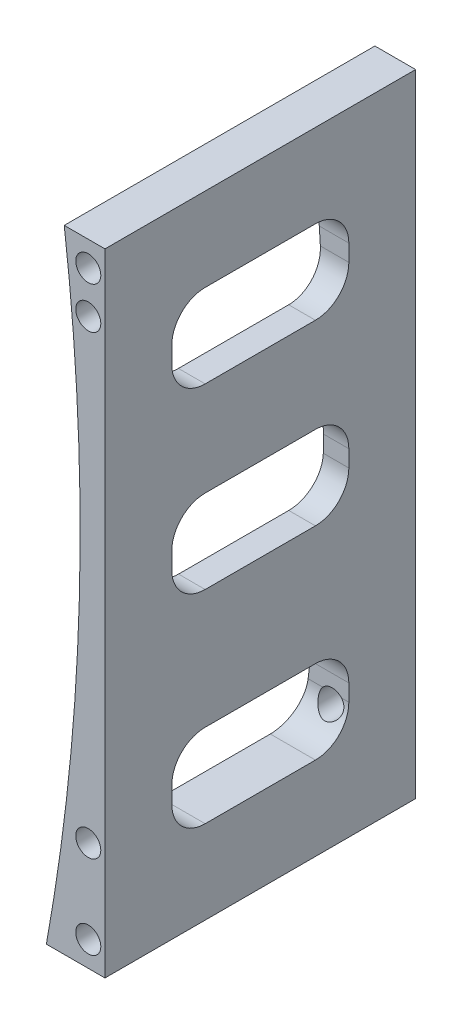
SolidWorks part; units mm, degrees
material "ABS"
ref_plane "Plano frontal" through (0, 0, 0) normal (0, 0, 1) x (1, 0, 0)
ref_plane "Plano superior" through (0, 0, 0) normal (0, 1, 0) x (1, 0, 0)
ref_plane "Plano direito" through (0, 0, 0) normal (1, 0, 0) x (0, 0, -1)
sketch "Esboço1" plane through (0, 0, 0) normal (0, 0, 1) x (1, 0, 0)
  line L0 (10, 0) -> (20, 0)
  line L1 (-20, 0) -> (-10, 0)
  line L2 (-16.3694, 93.6521) -> (-16.5765, 95.0244)
  arc A0 (-10, 0) -> (10, 0) centre (0, 0) ccw
  arc A1 (20, 0) -> (14.8299, 81.415) centre (263.5691, 56.3389) cw
  arc A2 (-20, 0) -> (-16.3694, 93.6521) centre (-263.5691, 56.3389) ccw
  arc A3 (14.8299, 81.415) -> (-16.4879, 94.4373) centre (3.2416, 97.7156) ccw
  dimension "D1" = 20
  dimension "D5" = 250
  dimension "D6" = 250
  dimension "D2" = 40
extrude "Ressalto-extrusão1" add sketch "Esboço1" along normal blind 37.2 contours A1 A3 L2 A2 L1 A0 L0 region at (0.9197, 55.6964, 0)
fillet "Filete3" radius 10 2 edges at (20, 0, 18.6) (-20, 0, 18.6)
fillet "Filete4" radius 10 2 edges at (-10, 0, 18.6) (10, 0, 18.6)
sketch "Esboço3" plane through (0, 0, 37.2) normal (0, 0, 1) x (1, 0, 0)
  line L1 (-34.3661, -10.4864) -> (30.1278, -10.4864)
  line L2 (-34.3661, -10.4864) -> (-34.3661, 11.5417)
  line L3 (-34.3661, 11.5417) -> (30.1278, 11.5417)
  line L4 (30.1278, -10.4864) -> (30.1278, 11.5417)
  dimension "D1" = 0
extrude "Corte-extrusão2" cut sketch "Esboço3" against normal through all
sketch "Esboço4" plane through (0, 0, 37.2) normal (0, 0, 1) x (1, 0, 0)
  line L0 (17.6155, 11.5417) -> (-17.6155, 11.5417) construction
  line L1 (-10.5979, 11.5417) -> (44.491, 11.5417)
  line L2 (-10.5979, 11.5417) -> (-10.5979, 134.6613)
  line L3 (-10.5979, 134.6613) -> (44.491, 134.6613)
  line L4 (44.491, 11.5417) -> (44.491, 134.6613)
  arc A0 (-17.6155, 11.5417) -> (-16.3694, 93.6521) centre (-263.5691, 56.3389) ccw construction
  point P9 (-13.5979, 52.5454)
  dimension "D1" = 3
extrude "Corte-extrusão3" cut sketch "Esboço4" against normal through all
sketch "Esboço5" plane through (0, 0, 37.2) normal (0, 0, 1) x (1, 0, 0)
  line L1 (-10.5979, 112.154) -> (-22.7536, 112.154)
  line L2 (-10.5979, 112.154) -> (-10.5979, 87.154)
  line L3 (-10.5979, 87.154) -> (-22.7536, 87.154)
  line L4 (-22.7536, 112.154) -> (-22.7536, 87.154)
  dimension "D1" = 25
extrude "Corte-extrusão4" cut sketch "Esboço5" against normal through all
sketch "Esboço6" plane through (-10.5979, 0, 0) normal (1, 0, 0) x (0, 0, -1)
  line L0 (0, 87.154) -> (-37.2, 87.154) construction
  line L1 (-25.2, 77.154) -> (-12, 77.154)
  line L2 (-29.2, 73.154) -> (-29.2, 71.154)
  line L3 (-25.2, 67.154) -> (-12, 67.154)
  line L4 (-8, 73.154) -> (-8, 71.154)
  line L5 (-25.2, 55.8317) -> (-12, 55.8317)
  line L6 (-29.2, 51.8317) -> (-29.2, 49.8317)
  line L7 (-25.2, 45.8317) -> (-12, 45.8317)
  line L8 (-8, 51.8317) -> (-8, 49.8317)
  line L9 (-25.2, 31.5417) -> (-12, 31.5417)
  line L10 (-29.2, 27.5417) -> (-29.2, 25.5417)
  line L11 (-25.2, 21.5417) -> (-12, 21.5417)
  line L12 (-8, 27.5417) -> (-8, 25.5417)
  line L13 (0, 11.5417) -> (-37.2, 11.5417) construction
  line L14 (0, 87.154) -> (0, 11.5417) construction
  line L15 (-37.2, 87.154) -> (-37.2, 11.5417) construction
  arc A0 (-12, 31.5417) -> (-8, 27.5417) centre (-12, 27.5417) cw
  arc A1 (-12, 21.5417) -> (-8, 25.5417) centre (-12, 25.5417) ccw
  arc A2 (-25.2, 31.5417) -> (-29.2, 27.5417) centre (-25.2, 27.5417) ccw
  arc A3 (-29.2, 25.5417) -> (-25.2, 21.5417) centre (-25.2, 25.5417) ccw
  arc A4 (-25.2, 55.8317) -> (-29.2, 51.8317) centre (-25.2, 51.8317) ccw
  arc A5 (-29.2, 49.8317) -> (-25.2, 45.8317) centre (-25.2, 49.8317) ccw
  arc A6 (-12, 55.8317) -> (-8, 51.8317) centre (-12, 51.8317) cw
  arc A7 (-12, 45.8317) -> (-8, 49.8317) centre (-12, 49.8317) ccw
  arc A8 (-12, 77.154) -> (-8, 73.154) centre (-12, 73.154) cw
  arc A9 (-12, 67.154) -> (-8, 71.154) centre (-12, 71.154) ccw
  arc A10 (-25.2, 77.154) -> (-29.2, 73.154) centre (-25.2, 73.154) ccw
  arc A11 (-29.2, 71.154) -> (-25.2, 67.154) centre (-25.2, 71.154) ccw
  dimension "D13" = 4
  dimension "D1" = 10
  dimension "D2" = 10
  dimension "D3" = 10
  dimension "D4" = 10
  dimension "D5" = 10
  dimension "D6" = 8
  dimension "D7" = 8
  dimension "D8" = 8
  dimension "D9" = 8
  dimension "D10" = 8
  dimension "D11" = 8
  dimension "D12" = 14.29
extrude "Corte-extrusão5" cut sketch "Esboço6" against normal through all
sketch "Esboço7" plane through (0, 0, 37.2) normal (0, 0, 1) x (1, 0, 0)
  line L0 (-15.4756, 87.154) -> (-10.5979, 87.154) construction
  line L1 (-10.5979, 87.154) -> (-10.5979, 11.5417) construction
  line L2 (-10.5979, 11.5417) -> (-17.6155, 11.5417) construction
  circle A0 centre (-12.5979, 14.5417) radius 1.5
  circle A1 centre (-12.5979, 84.154) radius 1.5
  circle A2 centre (-12.5979, 79.154) radius 1.5
  circle A3 centre (-12.5979, 24.5417) radius 1.5
  dimension "D1" = 3
  dimension "D2" = 3
  dimension "D3" = 3
  dimension "D4" = 5
  dimension "D5" = 2
  dimension "D6" = 2
  dimension "D7" = 2
  dimension "D8" = 2
  dimension "D9" = 3
  dimension "D10" = 3
  dimension "D11" = 3
  dimension "D12" = 10
extrude "Corte-extrusão6" cut sketch "Esboço7" against normal through all
